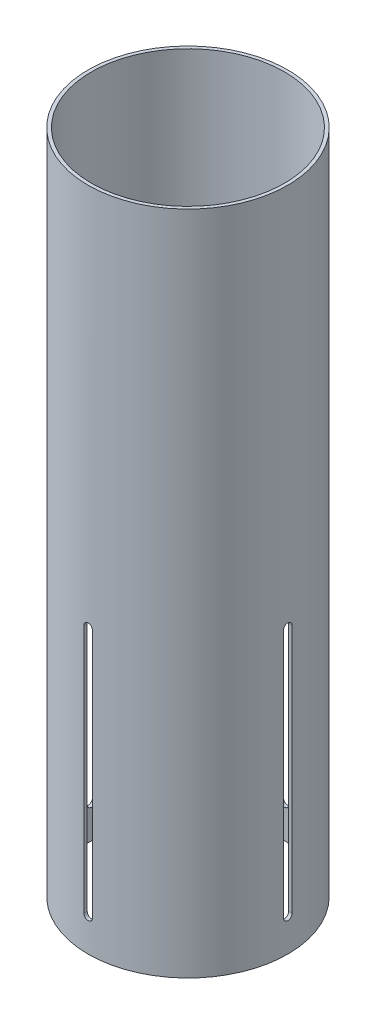
SolidWorks part; units mm, degrees
ref_plane "Front Plane" through (0, 0, 0) normal (0, 0, 1) x (1, 0, 0)
ref_plane "Top Plane" through (0, 0, 0) normal (0, 1, 0) x (1, 0, 0)
ref_plane "Right Plane" through (0, 0, 0) normal (1, 0, 0) x (0, 0, -1)
ref_axis "Axis1" through (0, -12.7, 0) along (0, 1, 0)
sketch "Sketch1" plane through (0, 0, 0) normal (0, 1, 0) x (1, 0, 0)
  circle A0 centre (0, 0) radius 38.1
  circle A1 centre (0, 0) radius 36.83
  dimension "D1" = 76.2
  dimension "D2" = 73.66
extrude "Boss-Extrude1" add sketch "Sketch1" along normal blind 254
sketch "Sketch2" plane through (0, 0, 0) normal (0, 0, 1) x (1, 0, 0)
  line L0 (0, 12.7) -> (0, 107.823) construction
  line L1 (-1.6193, 12.7) -> (-1.6193, 107.823)
  line L2 (1.6193, 12.7) -> (1.6193, 107.823)
  line L3 (-38.1, 0) -> (38.1, 0) construction
  arc A0 (-1.6193, 12.7) -> (1.6193, 12.7) centre (0, 12.7) ccw
  arc A1 (1.6193, 107.823) -> (-1.6193, 107.823) centre (0, 107.823) ccw
  point P3 (0, 60.2615)
  dimension "D2" = 12.7
  dimension "D3" = 95.123
  dimension "D1" = 3.2385
extrude "Cut-Extrude1" cut sketch "Sketch2" against normal through all and the other way through all
pattern_circular "CirPattern1" count 2 every 90 about axis through (0, -12.7, 0) along (0, 1, 0) of "Cut-Extrude1"
